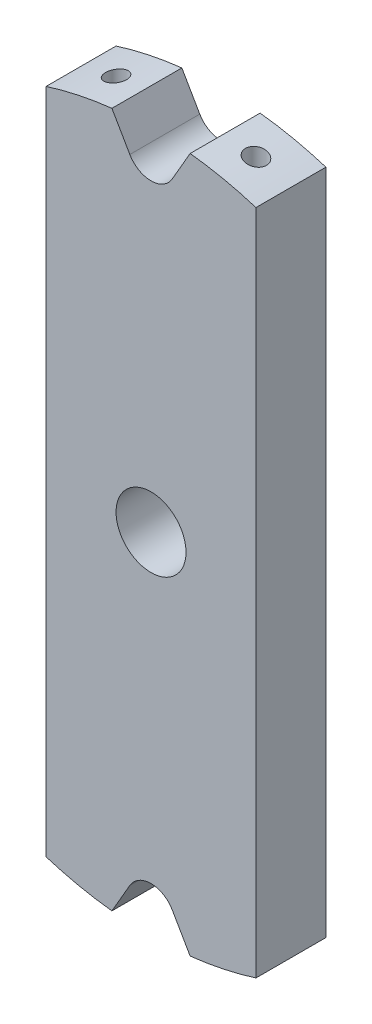
SolidWorks part; units mm, degrees
material "ABS"
ref_plane "前视基准面" through (0, 0, 0) normal (0, 0, 1) x (1, 0, 0)
ref_plane "上视基准面" through (0, 0, 0) normal (0, 1, 0) x (1, 0, 0)
ref_plane "右视基准面" through (0, 0, 0) normal (1, 0, 0) x (0, 0, -1)
sketch "草图1" plane through (0, 0, 0) normal (0, 0, 1) x (1, 0, 0)
  line L0 (0, 0) -> (0, 27.9405) construction
  line L1 (-15, 47.697) -> (-15, -47.697)
  line L2 (15, 47.697) -> (15, -47.697)
  line L3 (3.0311, 45.25) -> (5.5924, 49.6863)
  line L4 (-3.0311, 45.25) -> (-5.5924, 49.6863)
  line L5 (0, 0) -> (77.5321, 0) construction
  line L6 (-3.0311, -45.25) -> (-5.5924, -49.6863)
  line L7 (3.0311, -45.25) -> (5.5924, -49.6863)
  arc A0 (-15, -47.697) -> (15, -47.697) centre (0, 0) ccw
  arc A1 (15, 47.697) -> (-15, 47.697) centre (0, 0) ccw
  arc A3 (3.0311, 45.25) -> (-3.0311, 45.25) centre (0, 47) cw
  arc A4 (3.0311, -45.25) -> (-3.0311, -45.25) centre (0, -47) ccw
  dimension "D1" = 100
  dimension "D3" = 3.5
  dimension "D2" = 15
  dimension "D4" = 30
  dimension "D5" = 47
extrude "凸台-拉伸1" add sketch "草图1" along normal blind 10 contours A4 L7 A0 L2 A1 L3 A3 L4 L1 L6 region at (0, 0, 0)
sketch "草图2" plane through (0, 0, 0) normal (0, 1, 0) x (1, 0, 0)
  line L0 (0, -5) -> (15, -5) construction
  line L3 (15, -10) -> (15, 0) construction
  line L4 (15, -10) -> (15, 0) construction
  circle A0 centre (-10, -5) radius 1.5
  circle A1 centre (10, -5) radius 1.5
  point P3 (15, -5)
  dimension "D1" = 3
  dimension "D2" = 10
  dimension "D3" = 10
extrude "切除-拉伸1" cut sketch "草图2" against normal through all both and the other way through all
sketch "草图3" plane through (0, 0, 10) normal (0, 0, 1) x (1, 0, 0)
  circle A0 centre (0, 0) radius 5
  dimension "D1" = 10
extrude "切除-拉伸2" cut sketch "草图3" against normal through all and the other way through all
